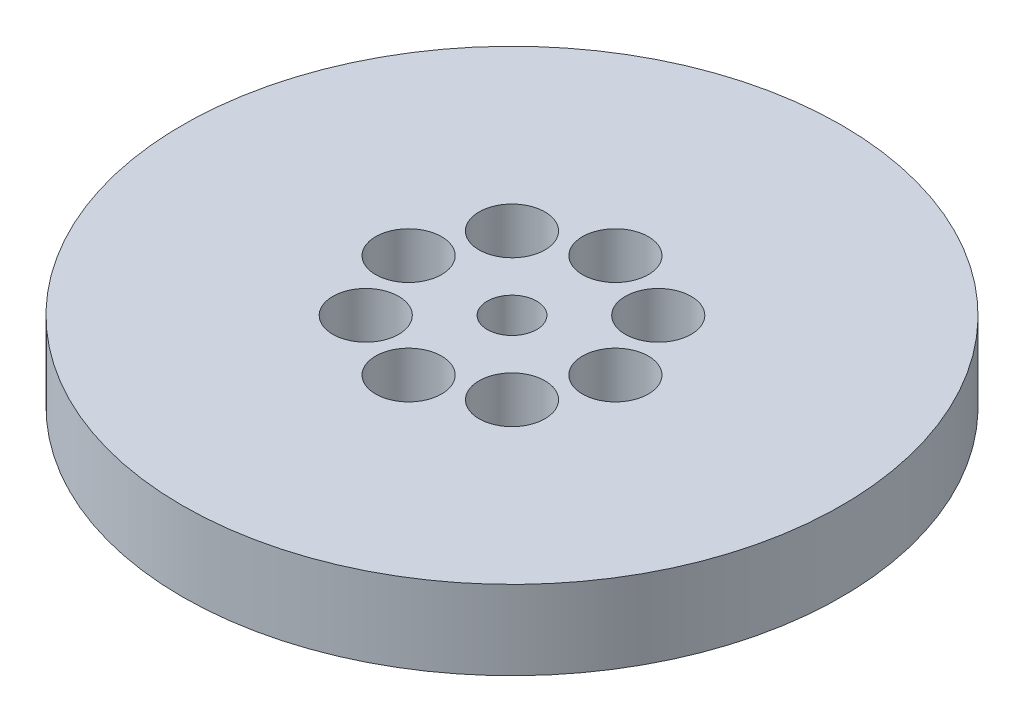
SolidWorks part; units mm, degrees
ref_plane "Front Plane" through (0, 0, 0) normal (0, 0, 1) x (1, 0, 0)
ref_plane "Top Plane" through (0, 0, 0) normal (0, 1, 0) x (1, 0, 0)
ref_plane "Right Plane" through (0, 0, 0) normal (1, 0, 0) x (0, 0, -1)
sketch "Sketch1" plane through (0, 0, 0) normal (0, 1, 0) x (1, 0, 0)
  circle A0 centre (0, 0) radius 100
  dimension "FLANGE_OD" = 200
extrude "Boss-Extrude1" add sketch "Sketch1" along normal blind 24
sketch "Sketch2" plane through (0, 0, 0) normal (0, 1, 0) x (1, 0, 0)
  circle A0 centre (0, 0) radius 7.5
  dimension "BORE_D" = 15
extrude "Cut-Extrude1" cut sketch "Sketch2" along normal through all
sketch "Sketch3" plane through (0, 24, 0) normal (0, 1, 0) x (1, 0, 0)
  circle A0 centre (0, 0) radius 31.378 construction
  circle A1 centre (-31.378, 0) radius 10
  dimension "BOLT_D" = 20
  dimension "BOLT_PCD" = 62.7559
extrude "Cut-Extrude2" cut sketch "Sketch3" against normal blind 20.9033
pattern_circular "CirPattern1" count 8 over 360 about axis through (0, 0, 0) along (0, 1, 0) of "Cut-Extrude2"
